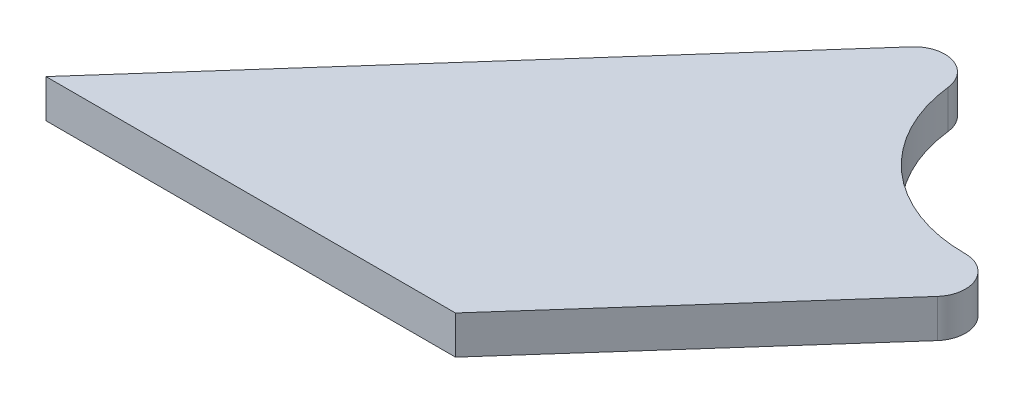
SolidWorks part; units mm, degrees
ref_plane "Front Plane" through (0, 0, 0) normal (0, 0, 1) x (1, 0, 0)
ref_plane "Top Plane" through (0, 0, 0) normal (0, 1, 0) x (1, 0, 0)
ref_plane "Right Plane" through (0, 0, 0) normal (1, 0, 0) x (0, 0, -1)
sketch "Sketch1" plane through (0, 0, 0) normal (0, 1, 0) x (1, 0, 0)
  line L0 (-9.498, 8.4307) -> (-50.8, -38.1)
  line L1 (-50.8, -38.1) -> (-16.8372, -38.1)
  line L2 (-16.8372, -38.1) -> (9.498, -8.4307)
  arc A0 (9.498, -8.4307) -> (-9.498, 8.4307) centre (0, 0) ccw
  dimension "D1" = 25.4
  dimension "D2" = 38.1
  dimension "D3" = 50.8
extrude "Boss-Extrude1" add sketch "Sketch1" along normal blind 3.175
sketch "Sketch2" plane through (0, 0, 0) normal (0, -1, 0) x (1, 0, 0)
  circle A0 centre (0, 0) radius 12.7
extrude "Cut-Extrude1" cut sketch "Sketch2" against normal through all
fillet "Fillet1" radius 2.54 2 edges at (-9.498, 1.5875, -8.4307) (9.498, 1.5875, 8.4307)
